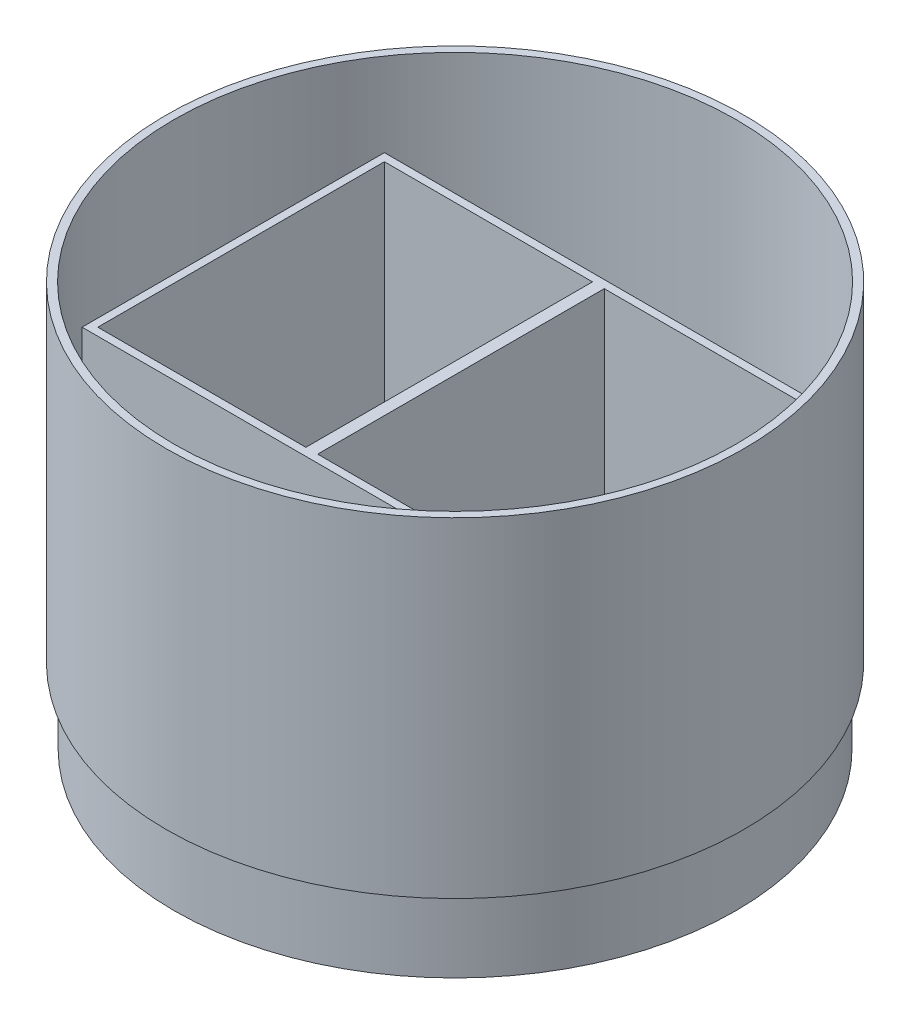
SolidWorks part; units mm, degrees
ref_plane "Front Plane" through (0, 0, 0) normal (0, 0, 1) x (1, 0, 0)
ref_plane "Top Plane" through (0, 0, 0) normal (0, 1, 0) x (1, 0, 0)
ref_plane "Right Plane" through (0, 0, 0) normal (1, 0, 0) x (0, 0, -1)
sketch "Sketch1" plane through (0, 0, 0) normal (0, 1, 0) x (1, 0, 0)
  circle A0 centre (0, 0) radius 35.75
  circle A1 centre (0, 0) radius 34.75
  dimension "D1" = 71.5
  dimension "D2" = 1
extrude "Boss-Extrude1" add sketch "Sketch1" along normal blind 9.5
sketch "Sketch3" plane through (0, 0, 0) normal (0, -1, 0) x (1, 0, 0)
  circle A2 centre (0, 0) radius 34.75 construction
  circle A3 centre (0, 0) radius 34.75
extrude "Boss-Extrude2" add sketch "Sketch3" against normal blind 2
sketch "Sketch4" plane through (0, 2, 0) normal (0, 1, 0) x (1, 0, 0)
  line L0 (0, 34.75) -> (0, -34.75) construction
  line L1 (-34.75, 0) -> (34.75, 0) construction
  line L2 (-28.25, 19.25) -> (-28.25, -19.25)
  line L3 (-27.25, 18.25) -> (-0.75, 18.25)
  line L4 (-27.25, 18.25) -> (-27.25, -18.25)
  line L5 (-27.25, -18.25) -> (-0.75, -18.25)
  line L6 (-0.75, 18.25) -> (-0.75, -18.25)
  line L7 (-27.25, 18.25) -> (-0.75, -18.25) construction
  line L8 (-27.25, -18.25) -> (-0.75, 18.25) construction
  line L9 (-28.25, -19.25) -> (0.25, -19.25)
  line L10 (0.25, 19.25) -> (0.25, -19.25)
  line L11 (-28.25, 19.25) -> (0.25, 19.25)
  circle A0 centre (0, 0) radius 34.75 construction
  circle A1 centre (0, 0) radius 34.75 construction
  point P9 (-14, 0)
  dimension "D1" = 26.5
  dimension "D2" = 36.5
  dimension "D3" = 14
  dimension "D4" = 1
extrude "Boss-Extrude3" add sketch "Sketch4" along normal blind 40
mirror "Mirror1" about plane through (0, 0, 0) normal (1, 0, 0) of "Boss-Extrude3"
sketch "Sketch2" plane through (0, 9.5, 0) normal (0, 1, 0) x (1, 0, 0)
  circle A0 centre (0, 0) radius 36.8
  circle A1 centre (0, 0) radius 34.75 construction
  circle A2 centre (0, 0) radius 34.75
  dimension "D1" = 73.6
extrude "Boss-Extrude4" add sketch "Sketch2" along normal blind 2
sketch "Sketch5" plane through (0, 11.5, 0) normal (0, 1, 0) x (1, 0, 0)
  circle A0 centre (0, 0) radius 36.8 construction
  circle A1 centre (0, 0) radius 36.8
  circle A2 centre (0, 0) radius 35.8
  dimension "D1" = 1
extrude "Boss-Extrude5" add sketch "Sketch5" along normal blind 40
